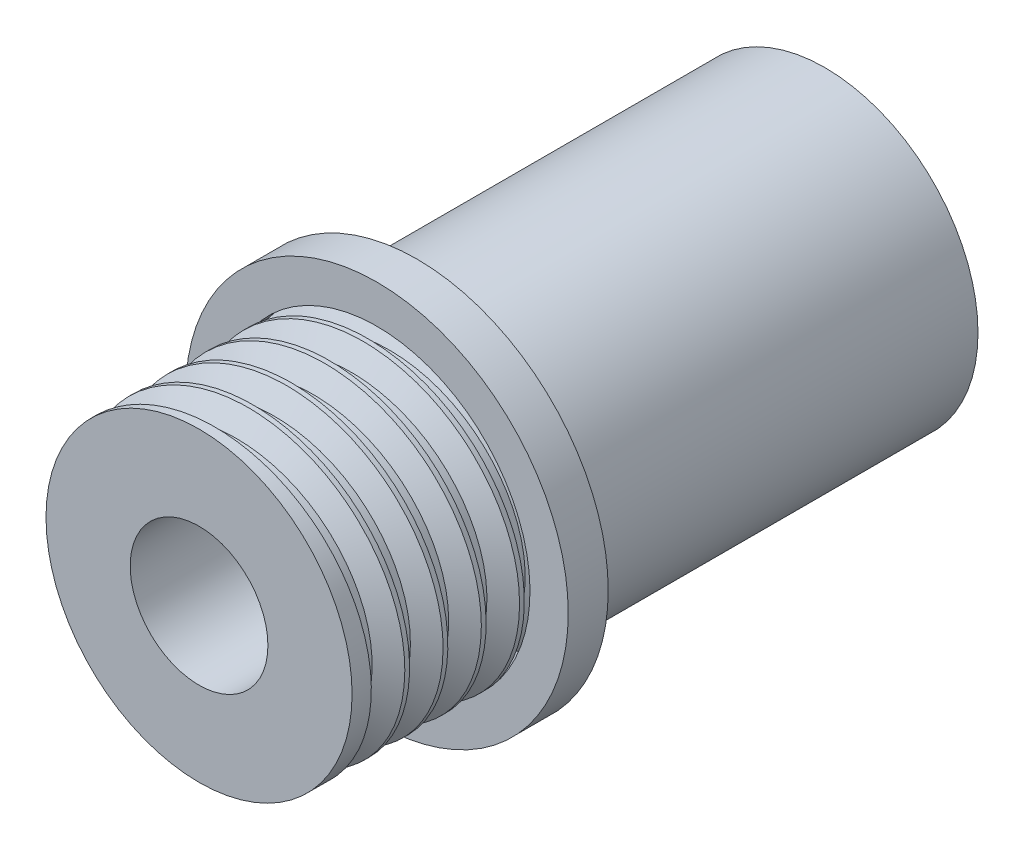
SolidWorks part; units mm, degrees
ref_plane "Front Plane" through (0, 0, 0) normal (0, 0, 1) x (1, 0, 0)
ref_plane "Top Plane" through (0, 0, 0) normal (0, 1, 0) x (1, 0, 0)
ref_plane "Right Plane" through (0, 0, 0) normal (1, 0, 0) x (0, 0, -1)
sketch "Sketch2" plane through (0, 0, 0) normal (1, 0, 0) x (0, 0, -1)
  line L0 (0, 0) -> (0, 4)
  line L1 (0, 4) -> (4.65, 4)
  line L2 (4.65, 4) -> (4.65, 5)
  line L3 (4.65, 5) -> (5.6946, 5)
  line L4 (5.6946, 5) -> (5.6946, 4)
  line L5 (5.6946, 4) -> (16.36, 4)
  line L6 (16.36, 4) -> (16.36, 0)
  line L7 (16.36, 0) -> (0, 0)
  dimension "D1" = 4.65
  dimension "D2" = 4
  dimension "D3" = 16.36
  dimension "D4" = 4
  dimension "D5" = 5
revolve "Revolve1" add sketch "Sketch2" angle 360 about L7
thread "Thread1" pitch 1 method cut profile "Thread Profile1" start angle 0, offset 0, length 4.6, pitch 1, diameter 8
ref_plane "Plane1" through (-4, 0, 0) normal (0, -1, 0) x (-1, 0, 0)
sketch "Thread Profile1" plane through (-4, 0, 0) normal (0, -1, 0) x (-1, 0, 0)
  line L0 (0, 0) -> (0, 1) construction
  line L11 (0, 0) -> (0, 0.875)
  line L12 (0, 0.875) -> (-0.5413, 0.5625)
  line L13 (-0.5413, 0.5625) -> (-0.5413, 0.3125)
  line L15 (-0.5413, 0.3125) -> (0, 0)
  line L17 (-0.5413, 0.4375) -> (0, 0.4375) construction
  point P2 (0, 0)
  dimension "Pitch" = 1
  dimension "Profile_Angle" = 60
  dimension "Profile_Land" = 0.25
  dimension "Profile_Height" = 0.5413
sketch "Sketch12" plane through (0, 0, 0) normal (0, 0, 1) x (1, 0, 0)
  circle A0 centre (0, 0) radius 1.8
  dimension "D1" = 3.6
extrude "Cut-Extrude1" cut sketch "Sketch12" against normal blind 10
